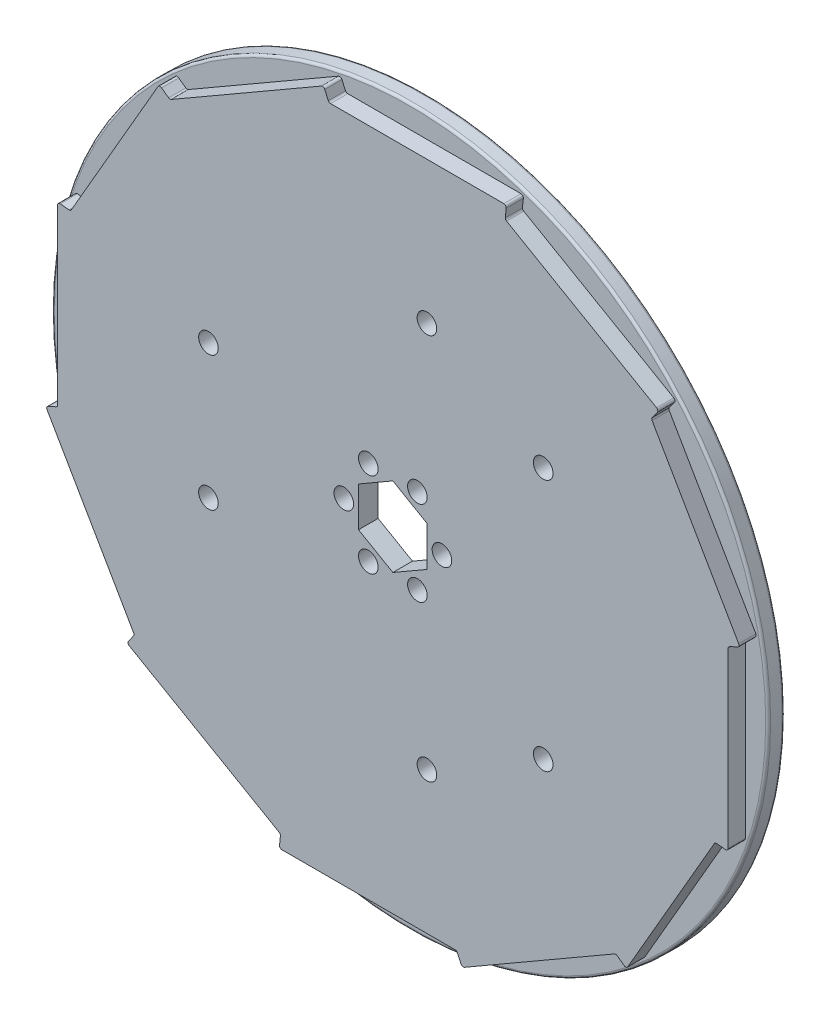
SolidWorks part; units mm, degrees
ref_plane "Front" through (0, 0, 0) normal (0, 0, 1) x (1, 0, 0)
ref_plane "Top" through (0, 0, 0) normal (0, 1, 0) x (1, 0, 0)
ref_plane "Right" through (0, 0, 0) normal (1, 0, 0) x (0, 0, -1)
sketch "Szkic1" plane through (0, 0, 0) normal (0, 0, 1) x (1, 0, 0)
  line L0 (0, 8.0829) -> (7, 4.0415)
  line L1 (-7, -4.0415) -> (-7, 4.0415)
  line L2 (0, -8.0829) -> (-7, -4.0415)
  line L3 (-7, 4.0415) -> (0, 8.0829)
  line L4 (7, -4.0415) -> (0, -8.0829)
  line L5 (7, 4.0415) -> (7, -4.0415)
  line L6 (0, -68.3372) -> (12.6961, -68.3372)
  line L7 (34.1686, -59.1817) -> (14.5884, -70.4864)
  line L8 (34.1686, -59.1817) -> (45.1637, -52.8337)
  line L9 (59.1817, -34.1686) -> (47.8771, -53.7488)
  line L10 (59.1817, -34.1686) -> (65.5298, -23.1735)
  line L11 (68.3372, 0) -> (68.3372, -22.6093)
  line L12 (68.3372, 0) -> (68.3372, 12.6961)
  line L13 (59.1817, 34.1686) -> (70.4864, 14.5884)
  line L14 (59.1817, 34.1686) -> (52.8337, 45.1637)
  line L15 (34.1686, 59.1817) -> (53.7488, 47.8771)
  line L16 (34.1686, 59.1817) -> (23.1735, 65.5298)
  line L17 (0, 68.3372) -> (22.6093, 68.3372)
  line L18 (0, 68.3372) -> (-12.6961, 68.3372)
  line L19 (-34.1686, 59.1817) -> (-14.5884, 70.4864)
  line L20 (-34.1686, 59.1817) -> (-45.1637, 52.8337)
  line L21 (-59.1817, 34.1686) -> (-47.8771, 53.7488)
  line L22 (-59.1817, 34.1686) -> (-65.5298, 23.1735)
  line L23 (-68.3372, 0) -> (-68.3372, 22.6093)
  line L24 (-68.3372, 0) -> (-68.3372, -12.6961)
  line L25 (-59.1817, -34.1686) -> (-70.4864, -14.5884)
  line L26 (-59.1817, -34.1686) -> (-52.8337, -45.1637)
  line L27 (-34.1686, -59.1817) -> (-53.7488, -47.8771)
  line L28 (-34.1686, -59.1817) -> (-23.1735, -65.5298)
  line L29 (0, -68.3372) -> (-22.6093, -68.3372)
  line L30 (-10, 0) -> (10, 0) construction
  line L31 (-5, 8.6603) -> (5, -8.6603) construction
  circle A0 centre (-37.5877, 13.6808) radius 2
  circle A1 centre (30.6418, 25.7115) radius 2
  circle A2 centre (-37.5877, -13.6808) radius 2
  circle A3 centre (6.9459, -39.3923) radius 2
  circle A4 centre (30.6418, -25.7115) radius 2
  circle A5 centre (6.9459, 39.3923) radius 2
  circle A6 centre (5, 8.6603) radius 2
  circle A7 centre (-10, 0) radius 2
  circle A8 centre (5, -8.6603) radius 2
  circle A9 centre (-5, 8.6603) radius 2
  circle A10 centre (-5, -8.6603) radius 2
  circle A11 centre (10, 0) radius 2
  arc A12 (13.8778, -70.248) -> (13.1475, -68.6222) centre (-23, -85.8372) ccw
  arc A13 (13.1475, -68.6222) -> (12.6961, -68.3372) centre (12.6961, -68.8372) ccw
  arc A14 (13.8778, -70.248) -> (14.5884, -70.4864) centre (14.3384, -70.0533) ccw
  arc A15 (47.1426, -53.8976) -> (45.6972, -52.8548) centre (23, -85.8372) ccw
  arc A16 (45.6972, -52.8548) -> (45.1637, -52.8337) centre (45.4137, -53.2667) ccw
  arc A17 (47.1426, -53.8976) -> (47.8771, -53.7488) centre (47.4441, -53.4988) ccw
  arc A18 (67.7755, -23.1054) -> (66.0023, -22.925) centre (62.8372, -62.8372) ccw
  arc A19 (66.0023, -22.925) -> (65.5298, -23.1735) centre (65.9628, -23.4235) ccw
  arc A20 (67.7755, -23.1054) -> (68.3372, -22.6093) centre (67.8372, -22.6093) ccw
  arc A21 (70.248, 13.8778) -> (68.6222, 13.1475) centre (85.8372, -23) ccw
  arc A22 (68.6222, 13.1475) -> (68.3372, 12.6961) centre (68.8372, 12.6961) ccw
  arc A23 (70.248, 13.8778) -> (70.4864, 14.5884) centre (70.0533, 14.3384) ccw
  arc A24 (53.8977, 47.1426) -> (52.8548, 45.6972) centre (85.8372, 23) ccw
  arc A25 (52.8548, 45.6972) -> (52.8337, 45.1637) centre (53.2667, 45.4137) ccw
  arc A26 (53.8977, 47.1426) -> (53.7488, 47.8771) centre (53.4988, 47.4441) ccw
  arc A27 (23.1054, 67.7755) -> (22.925, 66.0023) centre (62.8372, 62.8372) ccw
  arc A28 (22.925, 66.0023) -> (23.1735, 65.5298) centre (23.4235, 65.9628) ccw
  arc A29 (23.1054, 67.7755) -> (22.6093, 68.3372) centre (22.6093, 67.8372) ccw
  arc A30 (-13.8778, 70.248) -> (-13.1475, 68.6222) centre (23, 85.8372) ccw
  arc A31 (-13.1475, 68.6222) -> (-12.6961, 68.3372) centre (-12.6961, 68.8372) ccw
  arc A32 (-13.8778, 70.248) -> (-14.5884, 70.4864) centre (-14.3384, 70.0533) ccw
  arc A33 (-47.1426, 53.8977) -> (-45.6972, 52.8548) centre (-23, 85.8372) ccw
  arc A34 (-45.6972, 52.8548) -> (-45.1637, 52.8337) centre (-45.4137, 53.2667) ccw
  arc A35 (-47.1426, 53.8977) -> (-47.8771, 53.7488) centre (-47.4441, 53.4988) ccw
  arc A36 (-67.7755, 23.1054) -> (-66.0023, 22.925) centre (-62.8372, 62.8372) ccw
  arc A37 (-66.0023, 22.925) -> (-65.5298, 23.1735) centre (-65.9628, 23.4235) ccw
  arc A38 (-67.7755, 23.1054) -> (-68.3372, 22.6093) centre (-67.8372, 22.6093) ccw
  arc A39 (-70.248, -13.8778) -> (-68.6222, -13.1475) centre (-85.8372, 23) ccw
  arc A40 (-68.6222, -13.1475) -> (-68.3372, -12.6961) centre (-68.8372, -12.6961) ccw
  arc A41 (-70.248, -13.8778) -> (-70.4864, -14.5884) centre (-70.0533, -14.3384) ccw
  arc A42 (-53.8977, -47.1426) -> (-52.8548, -45.6972) centre (-85.8372, -23) ccw
  arc A43 (-52.8548, -45.6972) -> (-52.8337, -45.1637) centre (-53.2667, -45.4137) ccw
  arc A44 (-53.8977, -47.1426) -> (-53.7488, -47.8771) centre (-53.4988, -47.4441) ccw
  arc A45 (-23.1054, -67.7755) -> (-22.925, -66.0023) centre (-62.8372, -62.8372) ccw
  arc A46 (-22.925, -66.0023) -> (-23.1735, -65.5298) centre (-23.4235, -65.9628) ccw
  arc A47 (-23.1054, -67.7755) -> (-22.6093, -68.3372) centre (-22.6093, -67.8372) ccw
extrude "Dodanie-wyciągnięcie1" add sketch "Szkic1" along normal blind 4
sketch "Szkic2" plane through (0, 0, 4) normal (0, 0, 1) x (1, 0, 0)
  circle A0 centre (0, 0) radius 60
  circle A1 centre (0, 0) radius 73
  dimension "D1" = 120
  dimension "D2" = 146
extrude "Dodanie-wyciągnięcie2" add sketch "Szkic2" along normal blind 3
sketch "Szkic4" plane through (0, 0, 0) normal (0, 1, 0) x (1, 0, 0)
  line L0 (-60, -4) -> (-73, -7)
  line L1 (73, -4) -> (-73, -4) construction
  line L2 (-73, -7) -> (73, -7) construction
  line L3 (-73, -7) -> (-73, -11.5569)
  line L4 (-73, -11.5569) -> (-60, -11.5569)
  line L5 (-60, -11.5569) -> (-60, -4)
  line L6 (-60, -4) -> (-60, -7) construction
  line L7 (0, 0) -> (0, -30.6727) construction
revolve "Wycięcie-obrót1" cut sketch "Szkic4" angle 360 about L7
sketch "Szkic5" plane through (0, 0, 4) normal (0, 0, -1) x (-1, 0, 0)
  circle A0 centre (0, 0) radius 73
  circle A1 centre (0, 0) radius 60
extrude "Dodanie-wyciągnięcie3" add sketch "Szkic5" along normal blind 0.5
fillet "Zaokrąglenie2" radius 0.5 2 edges at (-73, 0, 7) (-73, 0, 3.5)
mirror "Lustro1" about plane through (-22.6093, -67.8372, 0) normal (0, 0, 1) of bodies 104
sketch "Szkic7" plane through (0, 0, 0) normal (0, 1, 0) x (1, 0, 0)
  line L1 (-77.2111, 0) -> (77.7418, 0)
  line L2 (-77.2111, 0) -> (-77.2111, -15.82)
  line L3 (-77.2111, -15.82) -> (77.7418, -15.82)
  line L4 (77.7418, 0) -> (77.7418, -15.82)
extrude "Wytnij-wyciągnięcie2" cut sketch "Szkic7" against normal through all both and the other way through all contours L3 L4 L1 L2
